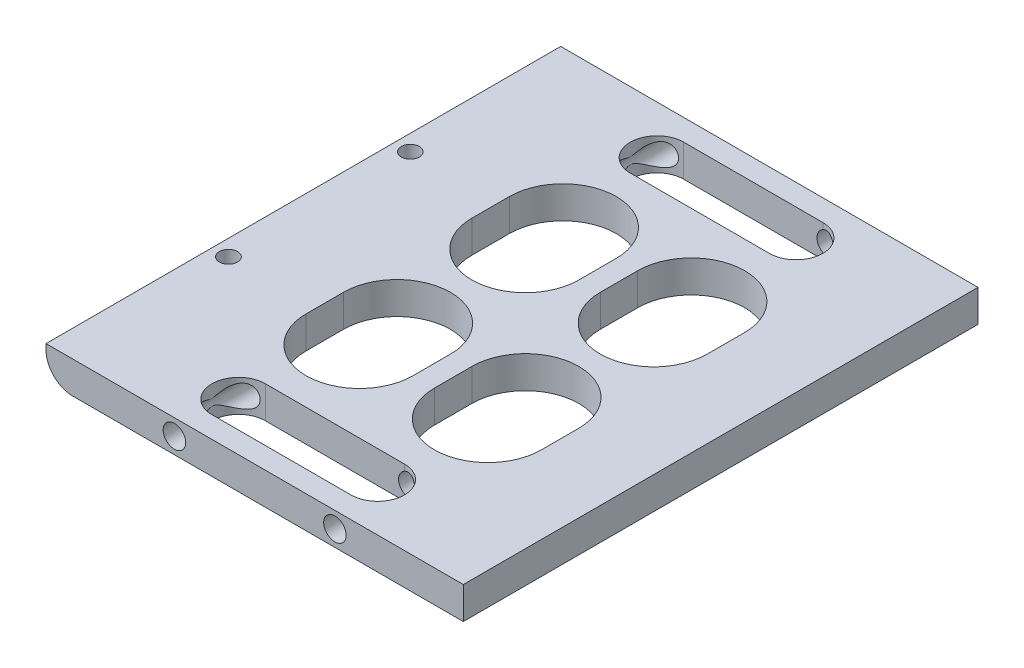
SolidWorks part; units mm, degrees
ref_plane "Front Plane" through (0, 0, 0) normal (1, 0, 0) x (0, 1, 0)
ref_plane "Top Plane" through (0, 0, 0) normal (0, 0, 1) x (0, 1, 0)
ref_plane "Right Plane" through (0, 0, 0) normal (0, 1, 0) x (-1, 0, 0)
sketch "Sketch1" plane through (0, 0, 0) normal (0, 1, 0) x (-1, 0, 0)
  line L0 (-49.4324, 0) -> (-18.4787, 0) construction
  line L1 (0, 0) -> (78, 0)
  line L2 (0, 0) -> (0, 96.2019)
  line L3 (0, 96.2019) -> (78, 96.2019)
  line L4 (78, 0) -> (78, 96.2019)
  point P33 (78, 96.2019)
  dimension "D1" = 96.2019
  dimension "D2" = 78
extrude "Boss-Extrude1" add sketch "Sketch1" along normal blind 6
sketch "Sketch2" plane through (0, 0, 0) normal (0, -1, 0) x (-1, 0, 0)
  line L0 (75, -31.101) -> (75, -65.1009) construction
  line L1 (78, 0) -> (78, -96.2019) construction
  line L2 (78, 0) -> (78, -96.2019)
  line L3 (78, 0) -> (72, 0)
  line L4 (0, 0) -> (78, 0) construction
  line L5 (72, 0) -> (72, -96.2019)
  line L6 (78, -96.2019) -> (0, -96.2019) construction
  line L7 (72, -96.2019) -> (78, -96.2019)
  line L8 (78, -48.1009) -> (72, -48.1009) construction
  circle A0 centre (75, -65.1009) radius 1.5
  circle A1 centre (75, -31.101) radius 1.5
  point P19 (75, -48.1009)
  dimension "D1" = 3
  dimension "D2" = 34
  dimension "D3" = 6
extrude "Cut-Extrude2" cut sketch "Sketch2" against normal through all contours A1 | A0 region at (-75, 0, 65.1009) region at (-75, 0, 31.101)
sketch "Sketch3" plane through (0, 0, 0) normal (0, 0, -1) x (1, 0, 0)
  line L0 (-39, 0) -> (-39, -6) construction
  line L1 (-54, -3) -> (-24, -3) construction
  line L2 (0, 0) -> (-78, 0) construction
  line L3 (0, -6) -> (-78, -6) construction
  circle A0 centre (-54, -3) radius 2.1
  circle A1 centre (-24, -3) radius 2.1
  point P6 (-39, -3)
  point P7 (0, 0)
  dimension "D1" = 4.2
  dimension "D2" = 30
extrude "Cut-Extrude3" cut sketch "Sketch3" against normal blind 18
extrude "Cut-Extrude4" cut sketch "Sketch3<2>" along normal blind 18 from surface starting at face at (-39, 3, 96.2019)
sketch "Sketch3<2>" plane through (0, 0, 0) normal (0, 0, -1) x (1, 0, 0) same geometry as "Sketch3"
fillet "Fillet1" radius 5 1 edges at (-78, 0, 48.1009)
sketch "Sketch4" plane through (0, 0, 0) normal (0, -1, 0) x (1, 0, 0)
  line L0 (-73, 48.1009) -> (0, 48.1009) construction
  line L5 (-73, 96.2019) -> (-73, 0) construction
  line L6 (0, 96.2019) -> (0, 0) construction
  line L7 (-36.5, 96.2019) -> (-36.5, 0) construction
  line L8 (-73, 96.2019) -> (0, 96.2019) construction
  line L9 (0, 0) -> (-73, 0) construction
  line L38 (-51, 87.2019) -> (-25, 87.2019) construction
  line L41 (-51, 92.2019) -> (-25, 92.2019)
  line L44 (-51, 82.2019) -> (-25, 82.2019)
  line L45 (-48.5, 29.1009) -> (-48.5, 36.1009) construction
  line L46 (-58.5, 29.1009) -> (-58.5, 36.1009)
  line L47 (-38.5, 29.1009) -> (-38.5, 36.1009)
  line L48 (-48.5, 67.101) -> (-48.5, 60.1009) construction
  line L49 (-38.5, 67.101) -> (-38.5, 60.1009)
  line L50 (-58.5, 67.101) -> (-58.5, 60.1009)
  line L51 (-24.5, 29.1009) -> (-24.5, 36.1009) construction
  line L52 (-14.5, 29.1009) -> (-14.5, 36.1009)
  line L53 (-34.5, 29.1009) -> (-34.5, 36.1009)
  line L54 (-24.5, 67.101) -> (-24.5, 60.1009) construction
  line L55 (-34.5, 67.101) -> (-34.5, 60.1009)
  line L56 (-14.5, 67.101) -> (-14.5, 60.1009)
  line L57 (-48.5, 50.1009) -> (-24.5, 50.1009) construction
  line L58 (-51, 9) -> (-25, 9) construction
  line L59 (-51, 4) -> (-25, 4)
  line L60 (-51, 14) -> (-25, 14)
  arc A20 (-51, 92.2019) -> (-51, 82.2019) centre (-51, 87.2019) ccw
  arc A21 (-25, 82.2019) -> (-25, 92.2019) centre (-25, 87.2019) ccw
  arc A22 (-58.5, 29.1009) -> (-38.5, 29.1009) centre (-48.5, 29.1009) ccw
  arc A23 (-38.5, 36.1009) -> (-58.5, 36.1009) centre (-48.5, 36.1009) ccw
  arc A24 (-38.5, 67.101) -> (-58.5, 67.101) centre (-48.5, 67.101) ccw
  arc A25 (-58.5, 60.1009) -> (-38.5, 60.1009) centre (-48.5, 60.1009) ccw
  arc A26 (-14.5, 29.1009) -> (-34.5, 29.1009) centre (-24.5, 29.1009) cw
  arc A27 (-34.5, 36.1009) -> (-14.5, 36.1009) centre (-24.5, 36.1009) cw
  arc A28 (-34.5, 67.101) -> (-14.5, 67.101) centre (-24.5, 67.101) cw
  arc A29 (-14.5, 60.1009) -> (-34.5, 60.1009) centre (-24.5, 60.1009) cw
  arc A30 (-51, 4) -> (-51, 14) centre (-51, 9) cw
  arc A31 (-25, 14) -> (-25, 4) centre (-25, 9) cw
  point P2 (-38, 87.2019)
  point P19 (-48.5, 32.6009)
  point P26 (-48.5, 63.601)
  point P31 (-34.0153, 88.1557)
  point P34 (0, 0)
  point P35 (-31, 87.1824)
  point P36 (0, 0)
  point P37 (-29, 85.7921)
  point P38 (-24.4217, 91.2145)
  point P41 (-38, 9)
  point P45 (-24.5, 32.6009)
  point P52 (-24.5, 63.601)
  dimension "D6" = 4
  dimension "D7" = 25
  dimension "D8" = 22
  dimension "D1" = 7
  dimension "D2" = 20
  dimension "D3" = 4
  dimension "D4" = 2
  dimension "D5" = 10
extrude "Cut-Extrude5" cut sketch "Sketch4" against normal blind 10
hole_wizard "CSK for M3 SFHCS2" positions "Sketch7" profile "Sketch8" countersink size "M3" standard "ANSI Metric" end condition through all
sketch "Sketch7" plane through (0, 0, 0) normal (0, -1, 0) x (-1, 0, 0)
  point P4 (75, -31.101)
  point P8 (75, -65.1009)
  point P16 (0, 0)
  point P17 (0, 0)
sketch "Sketch8" plane through (-75, 0, 31.101) normal (1, 0, 0) x (0, 0, -1)
  line L0 (0, 0) -> (0, 6)
  line L1 (0, 6) -> (1.7, 6)
  line L2 (1.7, 6) -> (1.7, 1.86)
  line L3 (1.7, 1.86) -> (3.56, 0)
  line L5 (3.56, 0) -> (0, 0)
  line L6 (-1.7, 1.86) -> (-3.56, 0) construction
  line L11 (0, -6.35) -> (0, 107.95) construction
  dimension "Thru Hole Dia." = 3.4
  dimension "Thru Hole Depth" = 6
  dimension "Near C'Sink Dia." = 7.12
  dimension "Near C'Sink Angle" = 90
equation "\"MotorDriverLength\"= 60mm"
equation "\"MotorLength\"= 60"
equation "\"MotorDriverWidth\"=44"
equation "\"MotorWidth\"= 37"
equation "\"InnerWallThickness\"=3"
equation "\"BatteryWidth\"= 60"
equation "\"OuterWallThickness\" = 6"
equation "\"CompartmentHeight\"=37"
equation "\"CompartmentWidth\"= \"MotorDriverLength\""
equation "\"MotorDiameter\"=37"
equation "\"BatteryHeight\"=24.2019"
equation "\"MotorDriverHeight\"=28"
equation "\"CircuitHeight\"=30"
equation "\"FanThickness\"= 10"
equation "\"FanHeight\"=50"
equation "\"MotorShaftHole\"=12"
equation "\"BearingBore\"=10"
equation "\"MinShinWidth\"= 20"
equation "\"ShinThickness\"=10"
equation "\"PivotDistance\"=30"
equation "\"ThighLength\"= 150"
equation "\"KneeLength\" =80"
equation "\"HipBore\"=27"
equation "\"ThighThickness\"=10"
equation "\"MaxBending\"=135"
equation "\"ShinLength\"=120"
equation "\"BearingDiameter\"= 10"
equation "\"CircuitLength\"=50"
equation "\"ChessisInnerWidth\"= \"OuterWallThickness\" * 2 + \"MotorDriverLength\" + \"MotorDiameter\" + \"InnerWallThickness\" * 3 + \"CircuitLength\""
equation "\"ChessisHeight\"= \"BatteryHeight\" + 10 + \"InnerWallThickness\" + \"MotorDiameter\" + 10 + \"OuterWallThickness\" * 2"
equation "\"ChassisWidth\"= \"MotorDriverWidth\"*4+30"
equation "\"D1@Sketch1\"=\"ChessisHeight\""
equation "\"D2@Sketch1\"=\"MotorWidth\"+\"FanThickness\"*2 +\"OuterWallThickness\"+15"
equation "\"D1@Boss-Extrude1\"=\"OuterWallThickness\""
equation "\"D2@Sketch2\"=17*2"
